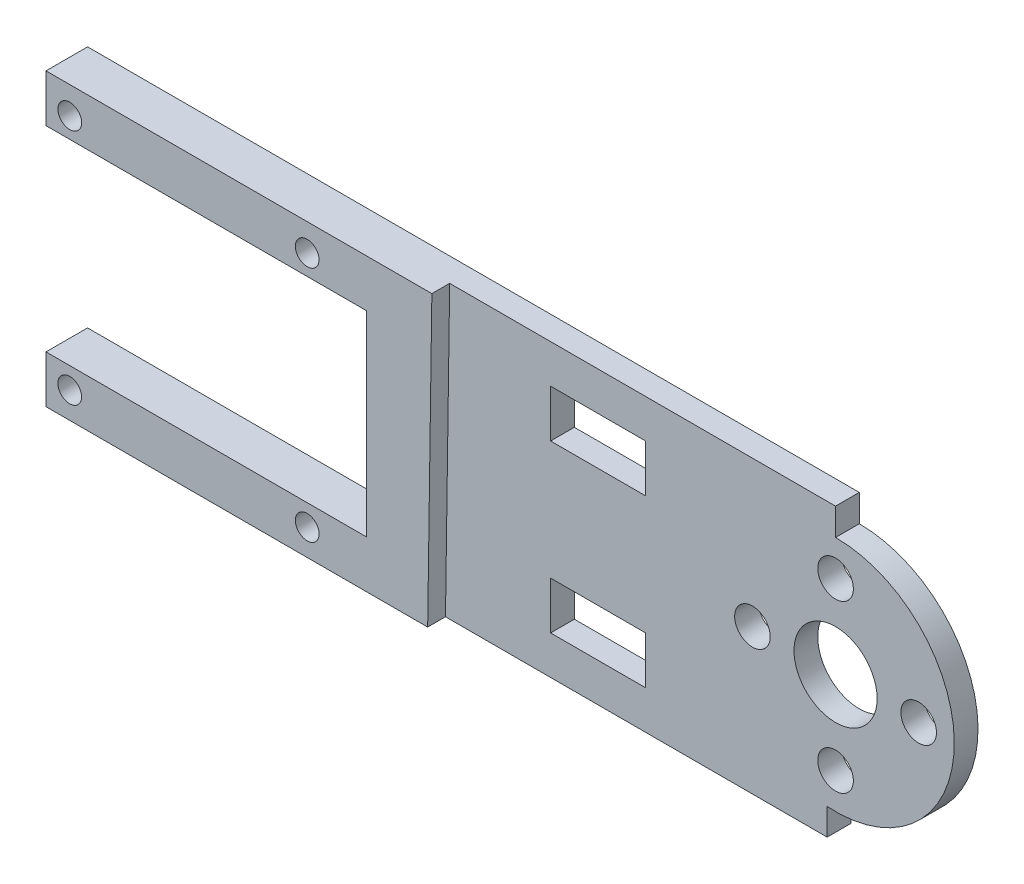
SolidWorks part; units mm, degrees
ref_plane "Front Plane" through (0, 0, 0) normal (0, 0, 1) x (1, 0, 0)
ref_plane "Top Plane" through (0, 0, 0) normal (0, 1, 0) x (1, 0, 0)
ref_plane "Right Plane" through (0, 0, 0) normal (1, 0, 0) x (0, 0, -1)
sketch "Sketch1" plane through (0, 0, 0) normal (0, 0, 1) x (1, 0, 0)
  line L1 (-4.8336, 12.25) -> (5.1664, 12.25)
  line L3 (-4.8336, -12.25) -> (5.1664, -12.25)
  line L5 (-4.8336, 12.25) -> (-24.8336, 12.25)
  line L6 (-24.8336, 12.25) -> (-24.8336, 8.25)
  line L12 (5.1664, 12.25) -> (40.1664, 12.25)
  line L13 (40.1664, 12.25) -> (40.1664, 9.9642)
  line L14 (39.4596, -12.25) -> (5.1664, -12.25)
  line L15 (-24.8336, 8.25) -> (2.1664, 8.25)
  line L16 (39.4596, -10.0108) -> (39.4596, -12.25)
  line L17 (16.1665, 9) -> (24.1665, 9)
  line L18 (16.1665, 9) -> (16.1665, 5)
  line L19 (16.1665, 5) -> (24.1665, 5)
  line L20 (24.1665, 9) -> (24.1665, 5)
  line L21 (16.1665, 9) -> (24.1665, 5) construction
  line L22 (16.1665, 5) -> (24.1665, 9) construction
  line L23 (16.1665, -5) -> (24.1665, -5)
  line L24 (16.1665, -5) -> (16.1665, -9)
  line L25 (16.1665, -9) -> (24.1665, -9)
  line L26 (24.1665, -5) -> (24.1665, -9)
  line L27 (16.1665, -5) -> (24.1665, -9) construction
  line L28 (16.1665, -9) -> (24.1665, -5) construction
  line L29 (2.1664, 8.25) -> (2.1664, -8.25)
  line L30 (2.1664, -8.25) -> (-24.8336, -8.25)
  line L31 (-24.8336, -8.25) -> (-24.8336, -12.25)
  line L32 (-24.8336, -12.25) -> (-4.8336, -12.25)
  arc A2 (39.4596, -10.0108) -> (40.1664, 9.9642) centre (40.1664, -0.0358) ccw
  circle A3 centre (40.1664, 6.9642) radius 1.5
  circle A4 centre (47.1664, -0.0358) radius 1.5
  circle A5 centre (40.1664, -7.0358) radius 1.5
  circle A6 centre (33.1664, -0.0358) radius 1.5
  circle A7 centre (40.1664, -0.0358) radius 3.5
  circle A8 centre (-2.8336, 9.9642) radius 1
  circle A9 centre (-2.8336, -10.0358) radius 1
  circle A10 centre (-22.8336, 9.9642) radius 1
  circle A11 centre (-22.8336, -10.0358) radius 1
  point P4 (0, 0)
  point P15 (0, 0)
  point P22 (20.1665, 7)
  point P35 (20.1665, -7)
  point P45 (0, 0)
  dimension "D3" = 2
  dimension "D4" = 2
  dimension "D11" = 20
  dimension "D12" = 3
  dimension "D15" = 7
  dimension "D8" = 2
  dimension "D16" = 2
  dimension "D5" = 43
  dimension "D6" = 24.5
  dimension "D7" = 24.5
  dimension "D9" = 12.25
  dimension "D10" = 35
  dimension "D13" = 7
  dimension "D17" = 20
  dimension "D18" = 5
  dimension "D19" = 20
  dimension "D20" = 4
  dimension "D21" = 4
  dimension "D22" = 8
  dimension "D23" = 8
  dimension "D24" = 10
  dimension "D25" = 10
  dimension "D26" = 20
  dimension "D27" = 20
  dimension "D28" = 4
  dimension "D29" = 4
  dimension "D14" = 4
extrude "Boss-Extrude1" add sketch "Sketch1" along normal blind 2
sketch "Sketch2" plane through (0, 0, 2) normal (0, 0, 1) x (1, 0, 0)
  line L0 (-24.8336, 12.25) -> (7.6664, 12.25)
  line L1 (40.1664, 12.25) -> (-24.8336, 12.25) construction
  line L2 (7.6664, 12.25) -> (7.313, -12.25)
  line L3 (-24.8336, -12.25) -> (39.4596, -12.25) construction
  line L4 (7.313, -12.25) -> (-24.8336, -12.25)
  line L5 (-24.8336, -12.25) -> (-24.8336, -8.25)
  line L6 (-24.8336, -8.25) -> (2.1664, -8.25)
  line L7 (2.1664, -8.25) -> (2.1664, 8.25)
  line L8 (2.1664, 8.25) -> (-24.8336, 8.25)
  line L9 (-24.8336, 8.25) -> (-24.8336, 12.25)
extrude "Boss-Extrude2" add sketch "Sketch2" along normal blind 1.5
sketch "Sketch4" plane through (0, 0, 0) normal (0, 0, -1) x (-1, 0, 0)
  circle A0 centre (2.8336, 9.9642) radius 1
  circle A1 centre (2.8336, -10.0358) radius 1
  circle A2 centre (22.8336, -10.0358) radius 1
  circle A3 centre (22.8336, 9.9642) radius 1
extrude "Cut-Extrude1" cut sketch "Sketch4" against normal through all
